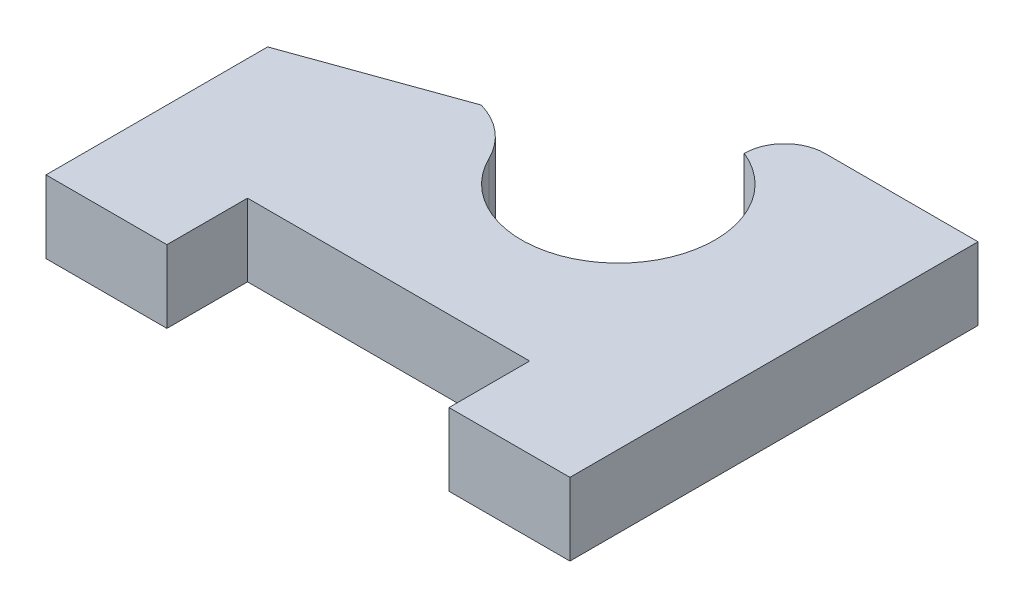
SolidWorks part; units mm, degrees
ref_plane "Front Plane" through (0, 0, 0) normal (0, 0, 1) x (1, 0, 0)
ref_plane "Top Plane" through (0, 0, 0) normal (0, 1, 0) x (1, 0, 0)
ref_plane "Right Plane" through (0, 0, 0) normal (1, 0, 0) x (0, 0, -1)
sketch "Sketch1" plane through (0, 0, 0) normal (0, 1, 0) x (1, 0, 0)
  line L0 (6.5, 2.5) -> (6.5, 0)
  line L1 (3.5, 0) -> (-3.5, 0)
  line L2 (-6.5, 0) -> (-6.5, 2.5)
  line L5 (-6.5, 2.5) -> (-6.5, 3.5)
  line L7 (6.5, 0) -> (6.5, -2)
  line L8 (6.5, -2) -> (3.5, -2)
  line L9 (3.5, 0) -> (3.5, -2)
  line L11 (-6.5, 0) -> (-6.5, -2)
  line L12 (-6.5, -2) -> (-3.5, -2)
  line L13 (-3.5, 0) -> (-3.5, -2)
  line L15 (6.5, 4.9) -> (6.5, 2.5)
  line L17 (-1.6, 4.9) -> (-2.6, 4.9)
  line L18 (-2.6, 4.9) -> (-6.5, 3.5)
  line L19 (1.7, 7.1249) -> (1.7, 8.1249)
  line L20 (1.7, 8.1249) -> (6.5, 8.1249)
  line L21 (6.5, 8.1249) -> (6.5, 4.9)
  arc A2 (-1.6, 4.9) -> (3.2, 4.9) centre (0.8, 4.9) ccw
  arc A3 (3.2, 4.9) -> (1.7, 7.1249) centre (0.8, 4.9) ccw
  point P0 (0, 0)
  dimension "D1" = 2.4
  dimension "D2" = 4.8
  dimension "D3" = 13
  dimension "D4" = 7.3
  dimension "D5" = 2.5
  dimension "D6" = 1
  dimension "D7" = 1
  dimension "D8" = 2
  dimension "D9" = 3
  dimension "D10" = 3.3
  dimension "D11" = 2.4
  dimension "D12" = 1
  dimension "D13" = 4.8
extrude "Boss-Extrude1" add sketch "Sketch1" along normal blind 1.8
fillet "Fillet1" radius 2 1 edges at (-1.6, 0.9, -4.9)
fillet "Fillet3" radius 1 1 edges at (1.7, 0.9, -8.1249)
ref_plane "Plane1" through (0, 0, 0) normal (0, -1, 0) x (-1, 0, 0)
